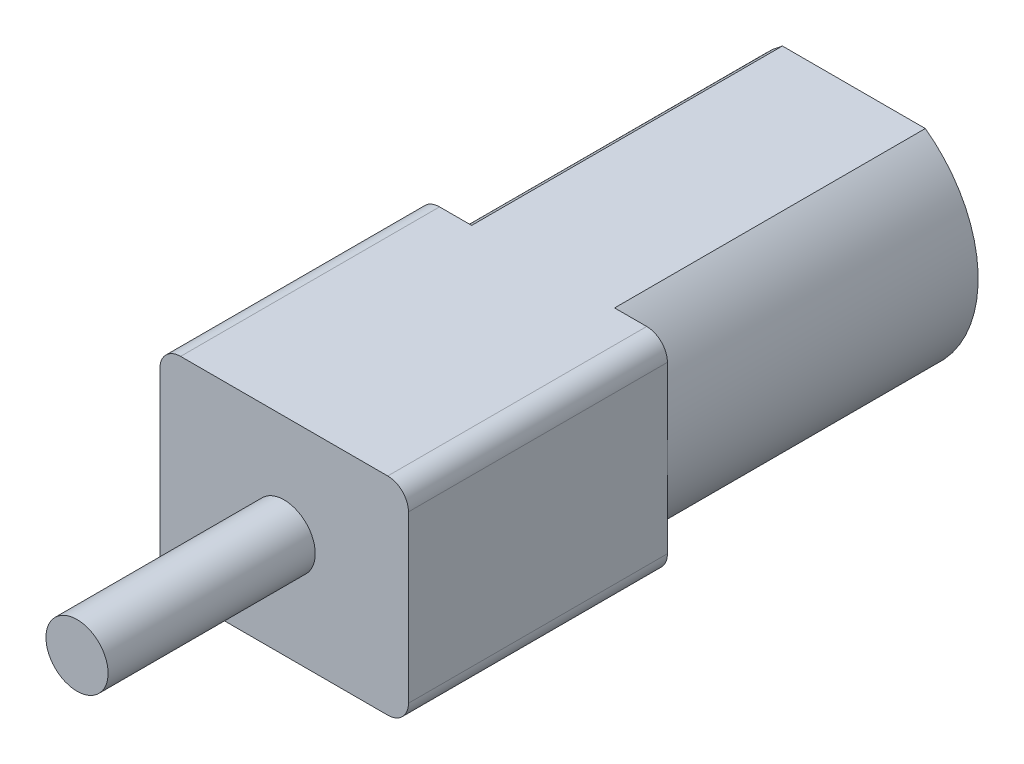
SolidWorks part; units mm, degrees
ref_plane "Front Plane" through (0, 0, 0) normal (0, 0, 1) x (1, 0, 0)
ref_plane "Top Plane" through (0, 0, 0) normal (0, 1, 0) x (1, 0, 0)
ref_plane "Right Plane" through (0, 0, 0) normal (1, 0, 0) x (0, 0, -1)
sketch "Sketch1" plane through (0, 0, 0) normal (0, 0, 1) x (1, 0, 0)
  line L1 (-3.45, 5) -> (3.45, 5)
  line L3 (-3.45, -5) -> (3.45, -5)
  line L5 (-6, 5) -> (6, -5) construction
  line L6 (-6, -5) -> (6, 5) construction
  line L11 (-3.45, 5) -> (3.45, -5) construction
  line L12 (-3.45, -5) -> (3.45, 5) construction
  arc A0 (-3.45, 5) -> (-3.45, -5) centre (0.177, 0) ccw
  arc A1 (3.45, 5) -> (3.45, -5) centre (-0.177, 0) cw
  point P0 (0, 0)
  point P6 (0, 0)
  dimension "D1" = 12
  dimension "D2" = 10
extrude "Boss-Extrude1" add sketch "Sketch1" along normal blind 15
sketch "Sketch2" plane through (0, 0, 15) normal (0, 0, 1) x (1, 0, 0)
  line L1 (-6, 5) -> (6, 5)
  line L2 (-6, 5) -> (-6, -5)
  line L3 (-6, -5) -> (6, -5)
  line L4 (6, 5) -> (6, -5)
  line L5 (-6, 5) -> (6, -5) construction
  line L6 (-6, -5) -> (6, 5) construction
  point P0 (0, 0)
  dimension "D1" = 10
  dimension "D2" = 12
extrude "Boss-Extrude2" add sketch "Sketch2" along normal blind 12.5
fillet "Fillet1" radius 1 4 edges at (6, 5, 21.25) (6, -5, 21.25) (-6, -5, 21.25) (-6, 5, 21.25)
sketch "Sketch3" plane through (0, 0, 27.5) normal (0, 0, 1) x (1, 0, 0)
  circle A0 centre (0, 0) radius 1.5
extrude "Boss-Extrude3" add sketch "Sketch3" along normal blind 10
sketch "Sketch4" plane through (0, 0, 0) normal (0, 0, -1) x (-1, 0, 0)
  circle A0 centre (0, 0) radius 2.5
  dimension "D1" = 5
extrude "Boss-Extrude4" add sketch "Sketch4" along normal blind 1.2
